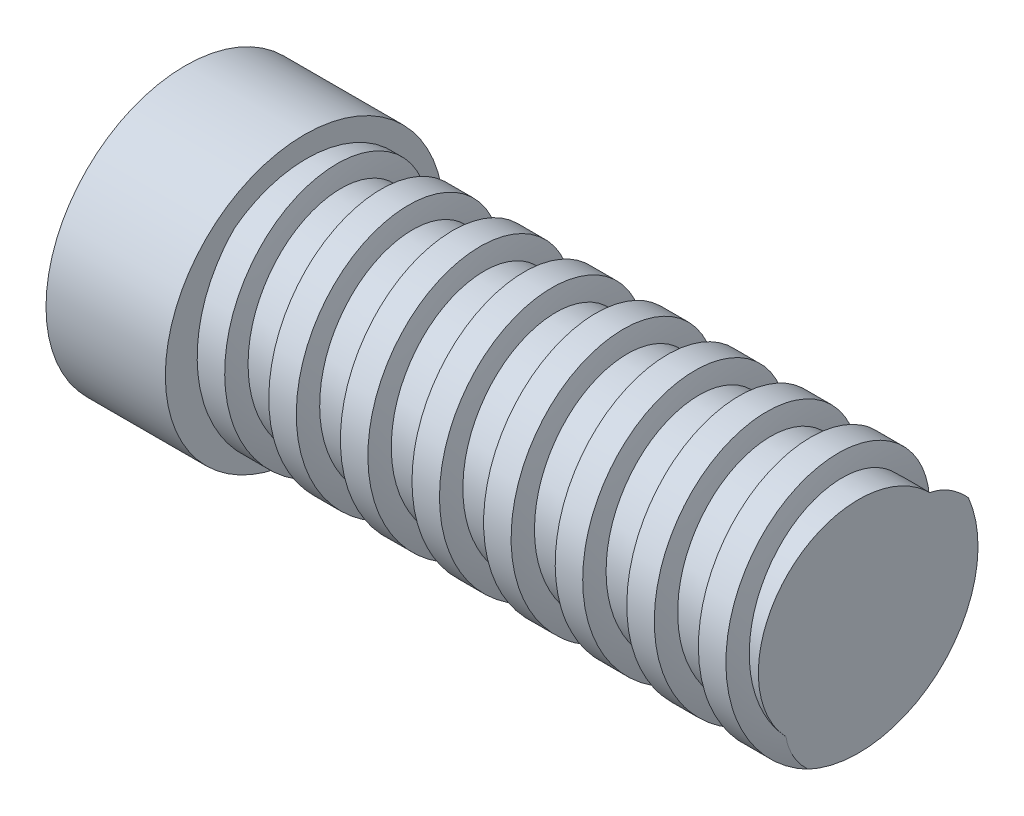
SolidWorks part; units mm, degrees
ref_plane "Piano frontale" through (0, 0, 0) normal (0, 0, 1) x (1, 0, 0)
ref_plane "Piano superiore" through (0, 0, 0) normal (0, 1, 0) x (1, 0, 0)
ref_plane "Piano destro" through (0, 0, 0) normal (1, 0, 0) x (0, 0, -1)
sketch "Schizzo1" plane through (0, 0, 0) normal (0, 0, 1) x (1, 0, 0)
  line L1 (3.0478, 1.2286) -> (21.0478, 1.2286)
  line L2 (3.0478, 1.2286) -> (3.0478, 4.2286)
  line L3 (3.0478, 4.2286) -> (21.0478, 4.2286)
  line L4 (21.0478, 1.2286) -> (21.0478, 4.2286)
  dimension "D1" = 18
  dimension "D2" = 3
revolve "Rivoluzione1" add sketch "Schizzo1" angle 360 about L1
sketch "Schizzo2" plane through (0, 0, 0) normal (0, 0, 1) x (1, 0, 0)
  line L0 (-3.0902, -11.7478) -> (-3.0902, 4.2522) construction
  line L1 (-2.5318, 4.2425) -> (1.2761, 3.1245) construction
  line L2 (-4.1212, 5.2754) -> (-2.0591, 5.2754)
  line L3 (-3.0902, -11.7478) -> (-2.5318, 4.2425) construction
  arc A2 (-2.6436, 3.7458) -> (-3.5368, 3.7458) centre (-3.0902, -11.7478) ccw
  arc A3 (-2.0591, 5.2754) -> (-2.6436, 3.7458) centre (1.2761, 3.1245) ccw
  arc A6 (-4.1212, 5.2754) -> (-3.5368, 3.7458) centre (-7.4565, 3.1245) cw
  point P1 (0, 0)
  dimension "D1" = 31
  dimension "D4" = 2
ref_plane "Piano1" through (24.0478, 0, 0) normal (1, 0, 0) x (0, 0, -1)
sketch "Schizzo3" plane through (24.0478, 0, 0) normal (1, 0, 0) x (0, 0, -1)
  circle A0 centre (0, 1.2286) radius 3 construction
  circle A1 centre (0, 1.2286) radius 3
curve "Elica/Spirale1" pitch 1.8 height 36 radius 3 centre (24.0478, 1.2286, 0) axis (-1, 0, 0) start towards (0, 0, 1)
sweep "Taglia-Sweep2" cut profiles "Schizzo2" path "Elica/Spirale1" align with end faces yes
sketch "Schizzo4" plane through (0, 0, 0) normal (0, 0, 1) x (1, 0, 0)
  line L0 (16.9301, 6.4536) -> (16.9301, -3.1913)
  line L1 (16.9301, -3.1913) -> (25.1287, -3.1913)
  line L2 (25.1287, -3.1913) -> (25.1287, 6.4536)
  line L3 (25.1287, 6.4536) -> (16.9301, 6.4536)
extrude "Taglio-Estrusione1" cut sketch "Schizzo4" along normal through all both and the other way through all
sketch "Schizzo5" plane through (0, 0, 0) normal (1, 0, 0) x (0, 0, -1)
  circle A0 centre (0, 1.2286) radius 3.5
  dimension "D1" = 7
extrude "Estrusione-Estrusione1" add sketch "Schizzo5" along normal blind 3 separate body
